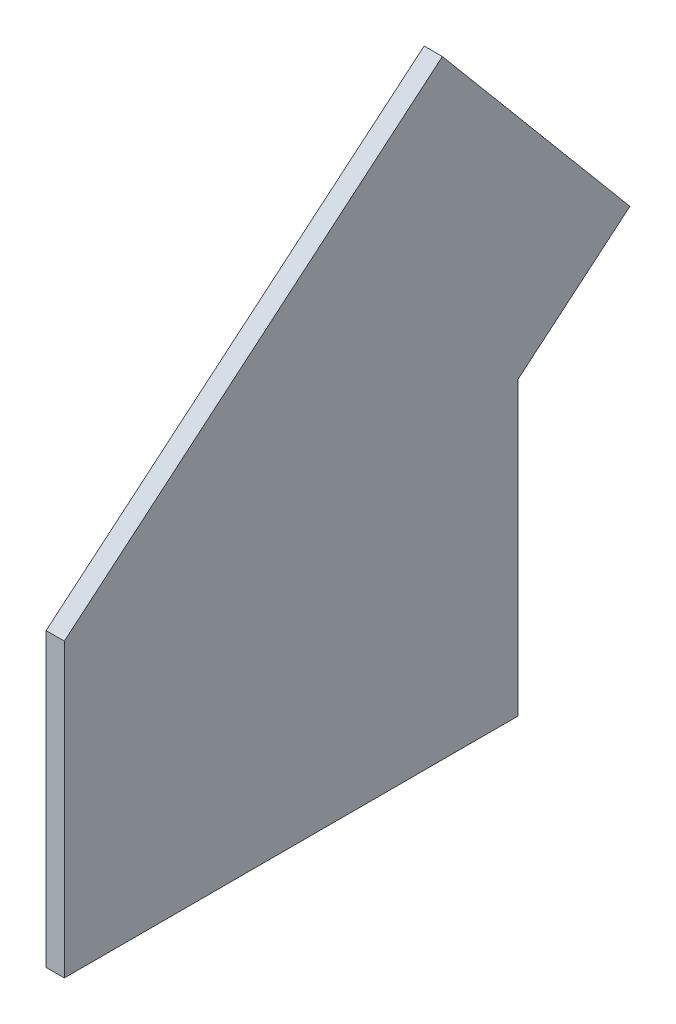
SolidWorks part; units mm, degrees
material "6061-T6 (SS)"
ref_plane "Front Plane" through (0, 0, 0) normal (0, 0, 1) x (1, 0, 0)
ref_plane "Top Plane" through (0, 0, 0) normal (0, 1, 0) x (1, 0, 0)
ref_plane "Right Plane" through (0, 0, 0) normal (1, 0, 0) x (0, 0, -1)
sketch "Sketch1" plane through (0, 0, 0) normal (1, 0, 0) x (0, 0, -1)
  line L0 (0, 0) -> (0, 50.8)
  line L2 (-13.1961, 106.0419) -> (-79.0308, 50.8)
  line L3 (-79.0308, 50.8) -> (-79.0308, 0)
  line L4 (-79.0308, 0) -> (0, 0)
  line L5 (0, 50.8) -> (19.4575, 67.1268)
  line L7 (-13.1961, 106.0419) -> (19.4575, 67.1268)
  line L8 (88.9, 188.3949) -> (-75.0792, 50.8) construction
  dimension "D1" = 50.8
  dimension "D3" = 50.8
  dimension "D4" = 25.4
extrude "Boss-Extrude1" add sketch "Sketch1" along normal blind 3.175
